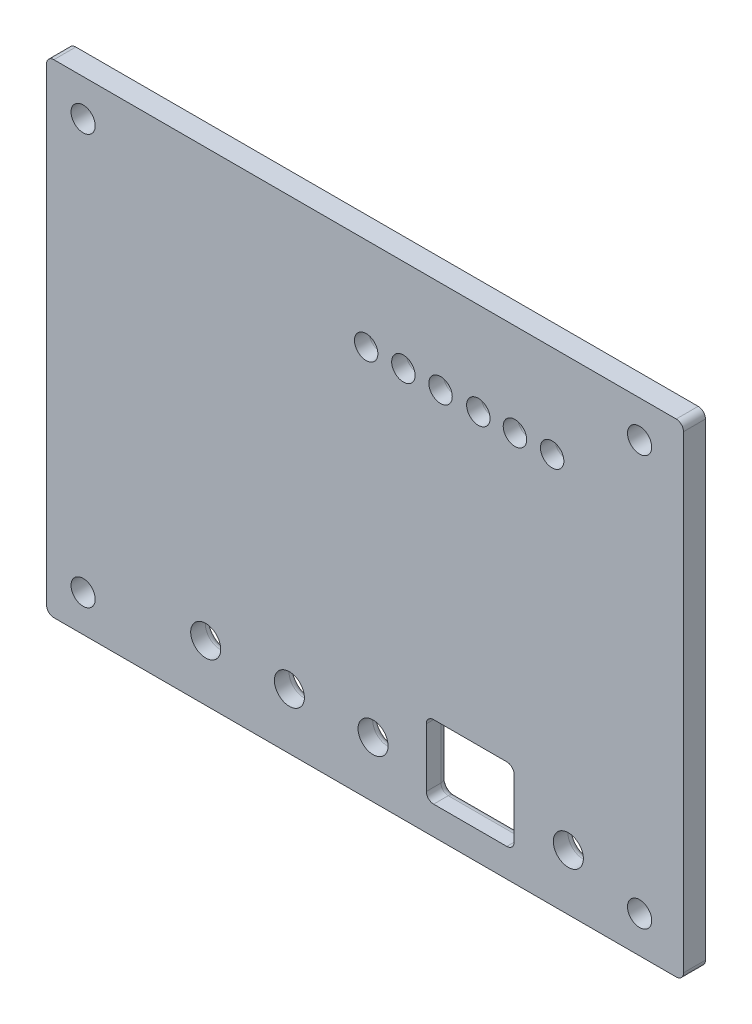
SolidWorks part; units mm, degrees
ref_plane "Спереди" through (0, 0, 0) normal (0, 0, 1) x (1, 0, 0)
ref_plane "Сверху" through (0, 0, 0) normal (0, 1, 0) x (1, 0, 0)
ref_plane "Справа" through (0, 0, 0) normal (1, 0, 0) x (0, 0, -1)
other "Configuration Table"
sketch "Эскиз1" plane through (0, 0, 0) normal (0, 0, 1) x (1, 0, 0)
  line L1 (43.5, -33) -> (-43.5, -33)
  line L2 (43.5, -33) -> (43.5, 33)
  line L3 (43.5, 33) -> (-43.5, 33)
  line L4 (-43.5, -33) -> (-43.5, 33)
  line L5 (43.5, -33) -> (-43.5, 33) construction
  line L6 (43.5, 33) -> (-43.5, -33) construction
  line L7 (8.37, -19.12) -> (20.37, -19.12)
  line L8 (8.37, -19.12) -> (8.37, -29.12)
  line L9 (8.37, -29.12) -> (20.37, -29.12)
  line L10 (20.37, -19.12) -> (20.37, -29.12)
  line L11 (8.37, -19.12) -> (20.37, -29.12) construction
  line L12 (8.37, -29.12) -> (20.37, -19.12) construction
  circle A0 centre (-38.5, 28) radius 1.65
  circle A1 centre (37.5, 28) radius 1.65
  circle A2 centre (37.5, -28) radius 1.65
  circle A3 centre (-38.5, -28) radius 1.65
  circle A4 centre (-21.76, -25.35) radius 2.05
  circle A5 centre (-10.33, -25.35) radius 2.05
  circle A6 centre (1.1, -25.35) radius 2.05
  circle A7 centre (27.77, -25.35) radius 2.05
  circle A8 centre (25.556, 20.34) radius 1.6
  circle A9 centre (20.476, 20.34) radius 1.6
  circle A10 centre (15.476, 20.34) radius 1.6
  circle A11 centre (10.316, 20.34) radius 1.6
  circle A12 centre (5.238, 20.34) radius 1.6
  circle A13 centre (0.156, 20.34) radius 1.6
  point P0 (0, 0)
  point P25 (14.37, -24.12)
  dimension "D3" = 5
  dimension "D7" = 6
  dimension "D20" = 53.34
  dimension "D22" = 63.976
  dimension "D23" = 58.976
  dimension "D24" = 53.816
  dimension "D25" = 48.738
  dimension "D26" = 43.656
  dimension "D1" = 87
  dimension "D2" = 66
  dimension "D4" = 5
  dimension "D5" = 5
  dimension "D6" = 5
  dimension "D8" = 5
  dimension "D9" = 5
  dimension "D10" = 6
  dimension "D12" = 21.74
  dimension "D13" = 7.65
  dimension "D14" = 11.43
  dimension "D15" = 11.43
  dimension "D16" = 12
  dimension "D17" = 10
  dimension "D18" = 71.27
  dimension "D19" = 3.88
  dimension "D21" = 69.056
  dimension "D27" = 51.87
extrude "Бобышка-Вытянуть1" add sketch "Эскиз1" along normal blind 3
fillet "Скругление1" radius 1 12 edges at (-43.5, -33, 1.5) (43.5, -33, 1.5) (43.5, 33, 1.5) (-43.5, 33, 1.5) (8.37, -29.12, 1.5) (8.37, -19.12, 1.5) (20.37, -19.12, 1.5) (20.37, -29.12, 1.5) (14.37, -29.12, 0) (8.37, -24.12, 0) (14.37, -19.12, 0) (20.37, -24.12, 0)
fillet "Скругление2" radius 1 10 edges at (27.156, 20.34, 0) (22.076, 20.34, 0) (17.076, 20.34, 0) (11.916, 20.34, 0) (6.838, 20.34, 0) (1.756, 20.34, 0) (-19.71, -25.35, 0) (-8.28, -25.35, 0) (3.15, -25.35, 0) (29.82, -25.35, 0)
sketch "Эскиз3" plane through (0, 0, 0) normal (0, 0, -1) x (-1, 0, 0)
  text T0 "ATARI" font "Arial" height in points 48
  text T1 "RESET" font "Arial Black" height in points 8
  text T2 "BOOT" font "Arial Black" height in points 10
  text T3 "<<" font "Arial Black" height in points 10
  text T4 ">>" font "Arial Black" height in points 10
  text T5 "4  3  2  1  W  R" font "Arial Black" height in points 10
  point P1 (0, 0)
  point P7 (0, 0)
  point P8 (0, 0)
  point P9 (0, 0)
extrude "Бобышка-Вытянуть2" add sketch "Эскиз3" along normal blind 0.8
